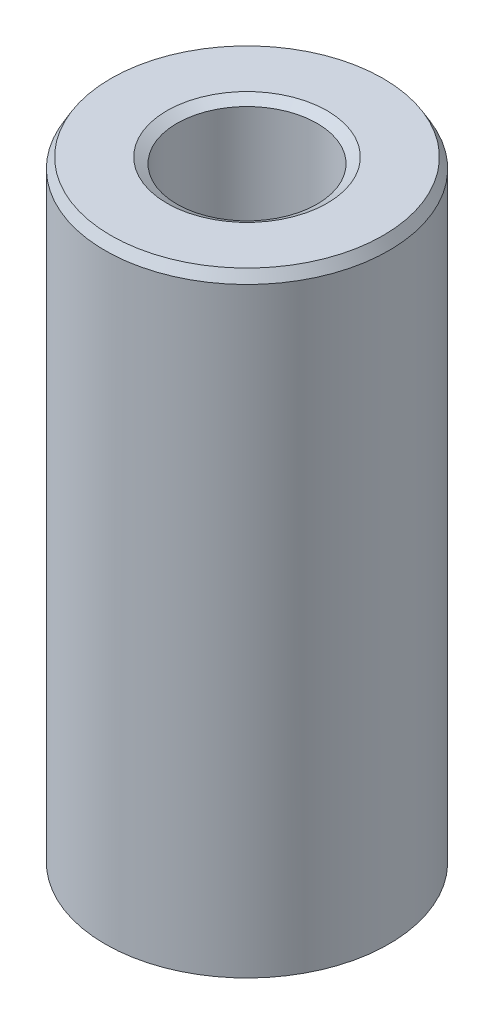
SolidWorks part; units mm, degrees
ref_plane "Front Plane" through (0, 0, 0) normal (0, 0, 1) x (1, 0, 0)
ref_plane "Top Plane" through (0, 0, 0) normal (0, 1, 0) x (1, 0, 0)
ref_plane "Right Plane" through (0, 0, 0) normal (1, 0, 0) x (0, 0, -1)
sketch "Sketch1" plane through (0, 0, 0) normal (0, 1, 0) x (1, 0, 0)
  circle A0 centre (0, 0) radius 5
  dimension "SLEEVE_OD" = 10
extrude "Boss-Extrude1" add sketch "Sketch1" along normal blind 21.7234
sketch "Sketch2" plane through (0, 0, 0) normal (0, 1, 0) x (1, 0, 0)
  circle A0 centre (0, 0) radius 2.4685
  dimension "BORE_D" = 4.937
extrude "Cut-Extrude1" cut sketch "Sketch2" along normal through all
chamfer "Chamfer1" distance 0.3561 angle 30 4 edges at (0, 21.7234, 2.4685) (0, 0, 2.4685) (0, 0, 5) (0, 21.7234, 5) first distance on face at (0, 21.7234, 2.4685) first distance on face at (0, 0, 2.4685) first distance on face at (0, 21.7234, 5)
